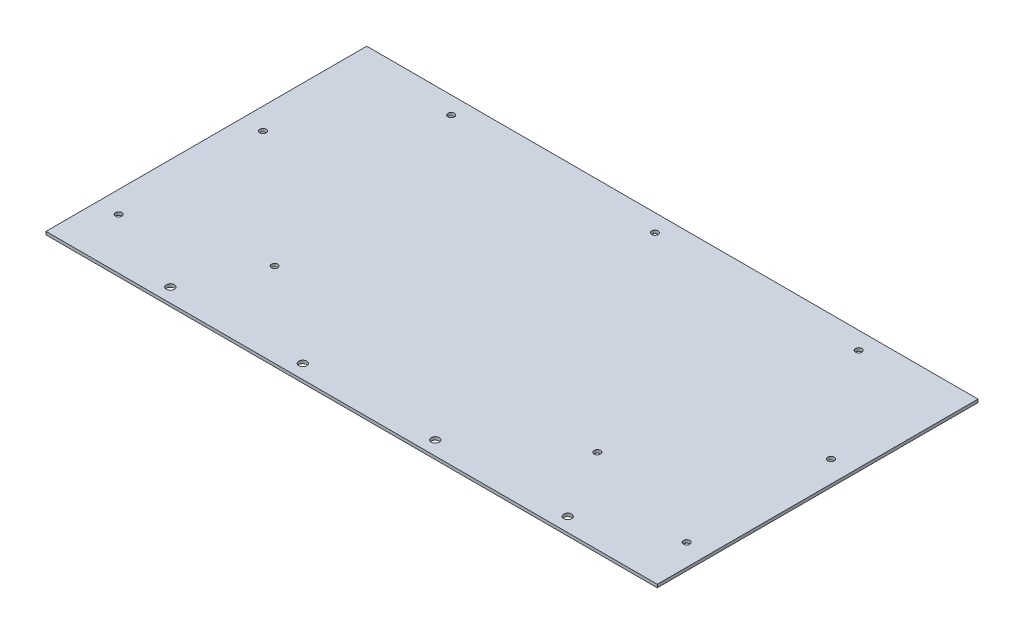
SolidWorks part; units mm, degrees
material "6061-T6 (SS)"
ref_plane "X-Y Datum" through (0, 0, 0) normal (0, 0, 1) x (1, 0, 0)
ref_plane "X-Z Datum" through (0, 0, 0) normal (0, 1, 0) x (1, 0, 0)
ref_plane "Y-Z Datum" through (0, 0, 0) normal (1, 0, 0) x (0, 0, -1)
sketch "Sketch1" plane through (0, 0, 0) normal (0, 0, 1) x (1, 0, 0)
  line L1 (-228.6115, -1.143) -> (228.6115, -1.143)
  line L2 (-228.6115, -1.143) -> (-228.6115, 1.143)
  line L3 (-228.6115, 1.143) -> (228.6115, 1.143)
  line L4 (228.6115, -1.143) -> (228.6115, 1.143)
  line L5 (-228.6115, -1.143) -> (228.6115, 1.143) construction
  line L6 (-228.6115, 1.143) -> (228.6115, -1.143) construction
  point P0 (0, 0)
  dimension "D1" = 2.286
  dimension "D2" = 457.223
extrude "Boss-Extrude1" add sketch "Sketch1" along normal blind 238.3152
sketch "Sketch2" plane through (0, 0, 0) normal (0, 0, -1) x (-1, 0, 0)
  line L22 (-228.6115, 1.143) -> (-228.6115, -1.143)
  line L23 (-228.6115, -1.143) -> (228.6115, -1.143)
  line L24 (228.6115, -1.143) -> (228.6115, 1.143)
  line L25 (228.6115, 1.143) -> (-228.6115, 1.143)
  line L26 (-228.6115, 1.143) -> (-228.6115, -1.143)
  line L27 (-228.6115, -1.143) -> (228.6115, -1.143)
  line L28 (228.6115, -1.143) -> (228.6115, 1.143)
  line L29 (228.6115, 1.143) -> (-228.6115, 1.143)
  dimension "D1" = 0
extrude "Boss-Extrude2" [suppressed] add sketch "Sketch2" along normal blind 3.175
sketch "Sketch9" plane through (0, 1.143, 0) normal (0, 1, 0) x (1, 0, 0)
  line L0 (-146.0615, -238.3152) -> (-146.0615, -229.4252) construction
  line L1 (228.6115, -238.3152) -> (-228.6115, -238.3152) construction
  line L2 (-228.6115, -238.3152) -> (-228.6115, 0) construction
  circle A0 centre (-146.0615, -229.4252) radius 3
  dimension "D2" = 82.55
  dimension "D3" = 6
  dimension "D1" = 8.89
extrude "Cut-Extrude10" cut sketch "Sketch9" against normal blind 2.54
pattern_linear "LPattern1" count 4 spacing 99.06 along (1, 0, 0) of "Cut-Extrude10"
sketch "Sketch10" plane through (0, -1.143, 0) normal (0, -1, 0) x (1, 0, 0)
  circle A0 centre (151.1185, 229.4252) radius 3 construction
  circle A1 centre (52.0585, 229.4252) radius 3 construction
  circle A2 centre (-47.0015, 229.4252) radius 3 construction
  circle A3 centre (-146.0615, 229.4252) radius 3 construction
  circle A4 centre (151.1185, 229.4252) radius 3
  circle A5 centre (52.0585, 229.4252) radius 3
  circle A6 centre (-47.0015, 229.4252) radius 3
  circle A7 centre (-146.0615, 229.4252) radius 3
sketch "Sketch15" plane through (0, 0, 238.3152) normal (0, 0, 1) x (1, 0, 0)
  line L4 (228.6115, -1.143) -> (228.6115, 1.143)
  line L5 (228.6115, 1.143) -> (-228.6115, 1.143)
  line L6 (-228.6115, 1.143) -> (-228.6115, -1.143)
  line L7 (-228.6115, -1.143) -> (228.6115, -1.143)
  line L8 (228.6115, -1.143) -> (228.6115, 1.143)
  line L9 (228.6115, 1.143) -> (-228.6115, 1.143)
  line L10 (-228.6115, 1.143) -> (-228.6115, -1.143)
  line L11 (-228.6115, -1.143) -> (228.6115, -1.143)
  dimension "D1" = 0
extrude "Boss-Extrude3" add sketch "Sketch15" along normal blind 1.5875
sketch "Sketch17" plane through (0, -1.143, 0) normal (0, -1, 0) x (1, 0, 0)
  point P0 (-212.419, 201.7248)
  point P1 (-212.419, 93.7748)
  point P3 (-152.4, 13.0175)
  point P5 (0, 13.0175)
  point P7 (152.4, 13.0175)
  point P9 (212.419, 93.7748)
  point P11 (212.419, 201.7248)
  point P13 (120.65, 176.776)
  point P15 (-120.65, 176.776)
hole_wizard "M4 Clearance Hole1" positions "Sketch17" profile "Sketch18" hole size "M4" standard "ANSI Metric" end condition through all
sketch "Sketch18" plane through (-212.419, -1.143, 201.7248) normal (1, 0, 0) x (0, 0, -1)
  line L0 (0, 0) -> (0, 2.286)
  line L1 (0, 2.286) -> (2.4, 2.286)
  line L2 (2.4, 2.286) -> (2.4, 0)
  line L5 (2.4, 0) -> (0, 0)
  line L11 (0, -6.35) -> (0, 107.95) construction
  dimension "Thru Hole Dia." = 4.8
  dimension "Thru Hole Depth" = 2.286
